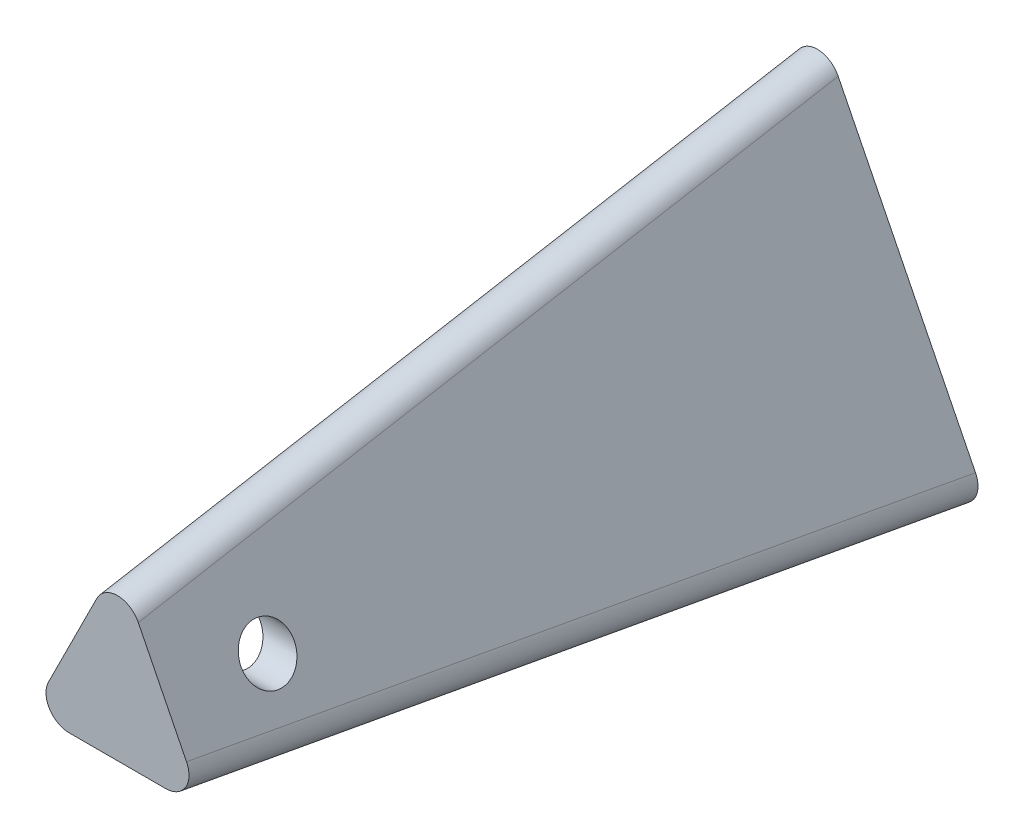
SolidWorks part; units mm, degrees
material "1060 Alloy"
ref_plane "Front Plane" through (0, 0, 0) normal (0, 0, 1) x (1, 0, 0)
ref_plane "Top Plane" through (0, 0, 0) normal (0, 1, 0) x (1, 0, 0)
ref_plane "Right Plane" through (0, 0, 0) normal (1, 0, 0) x (0, 0, -1)
sketch "Sketch1" plane through (0, 0, 0) normal (0, 0, 1) x (1, 0, 0)
  line L0 (19.05, 38.1) -> (0, 0)
  line L1 (0, 0) -> (38.1, 0)
  line L2 (38.1, 0) -> (19.05, 38.1)
  dimension "D1" = 38.1
  dimension "D2" = 38.1
extrude "Boss-Extrude1" add sketch "Sketch1" along normal blind 76.2 draft 4.5
shell "Shell1" thickness 3.302 removed face at (19.05, 2.9985, 38.1)
sketch "Sketch3" plane through (0, 0, 0) normal (1, 0, 0) x (0, 0, -1)
  line L0 (-76.2, 5.9971) -> (0, 0) construction
  line L1 (-76.2, 5.9971) -> (-76.2, 24.6901) construction
  circle A0 centre (-66.04, 14.115) radius 2.667
  dimension "D1" = 5.334
  dimension "D2" = 8.89
  dimension "D3" = 10.16
extrude "Cut-Extrude1" cut sketch "Sketch3" along normal through all
fillet "Fillet1" radius 2.54 3 edges at (33.2483, 2.9985, 38.1) (4.8517, 2.9985, 38.1) (19.05, 31.3951, 38.1)
sketch "Sketch4" plane through (0, 0, 72.898) normal (0, 0, -1) x (-1, 0, 0)
  line L0 (-19.05, 0) -> (-19.05, 22.8185)
  line L1 (-4.0971, 0) -> (-34.0029, 0) construction
  dimension "D1" = 22.8185
